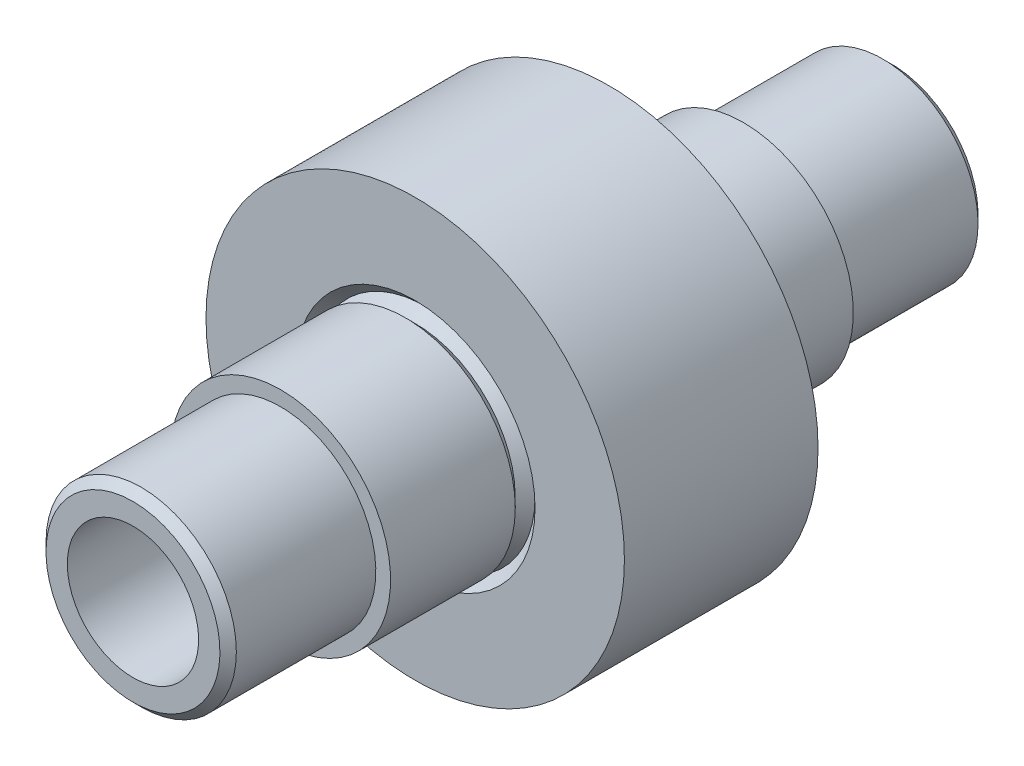
SolidWorks part; units mm, degrees
ref_plane "前视基准面" through (0, 0, 0) normal (0, 0, 1) x (1, 0, 0)
ref_plane "上视基准面" through (0, 0, 0) normal (0, 1, 0) x (1, 0, 0)
ref_plane "右视基准面" through (0, 0, 0) normal (1, 0, 0) x (0, 0, -1)
sketch "草图1" plane through (0, 0, 0) normal (1, 0, 0) x (0, 0, -1)
  line L0 (-25.6494, 0) -> (28.1258, 0) construction
  line L1 (-23.1, 0) -> (-23.1, 5.8)
  line L2 (-23.1, 5.8) -> (-14.1, 5.8)
  line L3 (-14.1, 5.8) -> (-14.1, 6.7) construction
  line L5 (-5.9, 6.7) -> (-5.9, 14)
  line L6 (-5.9, 14) -> (5.9, 14)
  line L7 (0, 14) -> (0, 0) construction
  line L8 (5.9, 6.7) -> (5.9, 14)
  line L9 (14.1, 6.7) -> (5.9, 6.7)
  line L10 (14.1, 5.8) -> (14.1, 6.7) construction
  line L11 (23.1, 5.8) -> (14.1, 5.8)
  line L12 (23.1, 0) -> (23.1, 5.8)
  line L13 (-23.1, 0) -> (23.1, 0)
  line L15 (-14.1, 6.7) -> (-5.9, 6.7) construction
  line L19 (14.1, 6.7) -> (14.1, 5.8)
  line L20 (-5.9, 6.7) -> (-14.1, 6.7)
  line L21 (-14.1, 6.7) -> (-14.1, 5.8)
  point P11 (-5.7982, 6.7)
  point P13 (0, 0)
  point P19 (0, 0)
  point P20 (0, 0)
  point P21 (0, 0)
  point P22 (10.7856, 6.7)
  point P23 (13.2719, 6.7)
  point P24 (-25.6494, 0)
  dimension "D1" = 5.8
  dimension "D2" = 11.8
  dimension "D3" = 14
  dimension "D4" = 9
  dimension "D5" = 8.2
  dimension "D6" = 6.7
  dimension "D7" = 46.2
revolve "旋转1" add sketch "草图1" angle 360 about L13
sketch "草图2" plane through (0, 0, 5.9) normal (0, 0, 1) x (1, 0, 0)
  line L0 (0, 0) -> (0, 10.5) construction
  circle A0 centre (0, 0) radius 10.5 construction
  circle A1 centre (0, 10.5) radius 1.5
  circle A2 centre (0, 0) radius 10.5 construction
  circle A3 centre (10.5, 0) radius 1.5
  circle A4 centre (0, 0) radius 10.5 construction
  circle A5 centre (0, -10.5) radius 1.5
  circle A6 centre (0, 0) radius 10.5 construction
  circle A7 centre (-10.5, 0) radius 1.5
  dimension "D1" = 21
  dimension "D2" = 3
  dimension "D3" = 4
extrude "切除-拉伸1" cut sketch "草图2" against normal through all
sketch "草图4" plane through (0, 0, -5.9) normal (0, 0, -1) x (-1, 0, 0)
  circle A0 centre (0, 0) radius 12.75
  circle A1 centre (0, 0) radius 14 construction
  circle A2 centre (0, 0) radius 14
  dimension "D1" = 25.5
extrude "切除-拉伸4" cut sketch "草图4" against normal through all
sketch "草图5" plane through (0, 0, -5.9) normal (0, 0, -1) x (-1, 0, 0)
  line L0 (-9.2687, 3.6181) -> (-8.332, 3.2525)
  line L1 (-3.6181, 9.2687) -> (-3.2525, 8.332)
  line L8 (3.6181, 9.2687) -> (3.2525, 8.332)
  line L9 (9.2687, 3.6181) -> (8.332, 3.2525)
  line L10 (9.2687, -3.6181) -> (8.332, -3.2525)
  line L11 (3.6181, -9.2687) -> (3.2525, -8.332)
  line L12 (-3.6181, -9.2687) -> (-3.2525, -8.332)
  line L13 (-9.2687, -3.6181) -> (-8.332, -3.2525)
  circle A2 centre (-10.5, 0) radius 1.5 construction
  circle A4 centre (0, 10.5) radius 1.5 construction
  arc A6 (-3.7191, 7.083) -> (-7.083, 3.7191) centre (0, 0) ccw
  arc A7 (-5.0046, 9.7956) -> (-9.7956, 5.0046) centre (0, 0) ccw
  arc A14 (-8.332, 3.2525) -> (-7.083, 3.7191) centre (-7.9683, 4.184) ccw
  arc A15 (-9.2687, 3.6181) -> (-9.7956, 5.0046) centre (-8.9051, 4.5497) cw
  arc A16 (-3.2525, 8.332) -> (-3.7191, 7.083) centre (-4.184, 7.9683) cw
  arc A17 (-3.6181, 9.2687) -> (-5.0046, 9.7956) centre (-4.5497, 8.9051) ccw
  arc A18 (3.6181, 9.2687) -> (5.0046, 9.7956) centre (4.5497, 8.9051) cw
  arc A19 (3.2525, 8.332) -> (3.7191, 7.083) centre (4.184, 7.9683) ccw
  arc A20 (7.083, 3.7191) -> (3.7191, 7.083) centre (0, 0) ccw
  arc A21 (8.332, 3.2525) -> (7.083, 3.7191) centre (7.9683, 4.184) cw
  arc A22 (9.2687, 3.6181) -> (9.7956, 5.0046) centre (8.9051, 4.5497) ccw
  arc A23 (9.7956, 5.0046) -> (5.0046, 9.7956) centre (0, 0) ccw
  arc A24 (9.2687, -3.6181) -> (9.7956, -5.0046) centre (8.9051, -4.5497) cw
  arc A25 (8.332, -3.2525) -> (7.083, -3.7191) centre (7.9683, -4.184) ccw
  arc A26 (3.7191, -7.083) -> (7.083, -3.7191) centre (0, 0) ccw
  arc A27 (3.2525, -8.332) -> (3.7191, -7.083) centre (4.184, -7.9683) cw
  arc A28 (3.6181, -9.2687) -> (5.0046, -9.7956) centre (4.5497, -8.9051) ccw
  arc A29 (5.0046, -9.7956) -> (9.7956, -5.0046) centre (0, 0) ccw
  arc A30 (-3.6181, -9.2687) -> (-5.0046, -9.7956) centre (-4.5497, -8.9051) cw
  arc A31 (-3.2525, -8.332) -> (-3.7191, -7.083) centre (-4.184, -7.9683) ccw
  arc A32 (-7.083, -3.7191) -> (-3.7191, -7.083) centre (0, 0) ccw
  arc A33 (-8.332, -3.2525) -> (-7.083, -3.7191) centre (-7.9683, -4.184) cw
  arc A34 (-9.2687, -3.6181) -> (-9.7956, -5.0046) centre (-8.9051, -4.5497) ccw
  arc A35 (-9.7956, -5.0046) -> (-5.0046, -9.7956) centre (0, 0) ccw
  point P23 (0, 0)
  point P25 (0, 0)
  point P27 (-10.247, 4)
  point P32 (-4, 10.247)
  point P44 (0, 0)
  point P57 (0, 0)
  point P63 (0, 0)
  dimension "D3" = 11
  dimension "D4" = 8
  dimension "D6" = 1
  dimension "D1" = 4
  dimension "D2" = 4
extrude "切除-拉伸5" cut sketch "草图5" against normal through all
sketch "草图6" plane through (0, 0, -23.1) normal (0, 0, -1) x (-1, 0, 0)
  circle A0 centre (0, 0) radius 4
  dimension "D1" = 8
extrude "切除-拉伸6" cut sketch "草图6" against normal through all
sketch "草图7" plane through (0, 0, -5.9) normal (0, 0, -1) x (-1, 0, 0)
  circle A1 centre (0, 0) radius 12.75
  circle A2 centre (0, 0) radius 12.75
  circle A5 centre (0, 0) radius 6.7
  circle A6 centre (0, 0) radius 6.7
  dimension "D1" = 0
  dimension "D2" = 0
extrude "凸台-拉伸1" add sketch "草图7" against normal up to surface (11.8 mm away) up to face at (0, -6.7, 5.9)
sketch "草图8" plane through (0, 0, 0) normal (1, 0, 0) x (0, 0, -1)
  line L0 (-6.5021, 6.7) -> (-5.9, 6.0932)
  line L1 (-5.9, 6.7) -> (-14.1, 6.7) construction
  line L2 (-5.9, 12.75) -> (-5.9, -12.75) construction
  line L3 (-5.9, 6.0932) -> (-5.2948, 6.7)
  line L4 (-5.2948, 6.7) -> (-5.9, 7.3037)
  line L5 (0, 0) -> (13.1023, 0) construction
  line L6 (-6.5021, 6.7) -> (-5.9, 7.3037)
  line L7 (0, 0) -> (0, 5.093) construction
  line L8 (6.5021, 6.7) -> (5.9, 7.3037)
  line L9 (5.2948, 6.7) -> (5.9, 7.3037)
  line L10 (5.9, 6.0932) -> (5.2948, 6.7)
  line L11 (6.5021, 6.7) -> (5.9, 6.0932)
revolve "切除-旋转1" cut sketch "草图8" angle 360 about L5
chamfer "倒角1" distance 0.5 angle 45 2 edges at (0, -5.8, -23.1) (0, -5.8, 23.1)
move or copy body "实体-移动/复制1" [suppressed] bodies to move or copy 113
